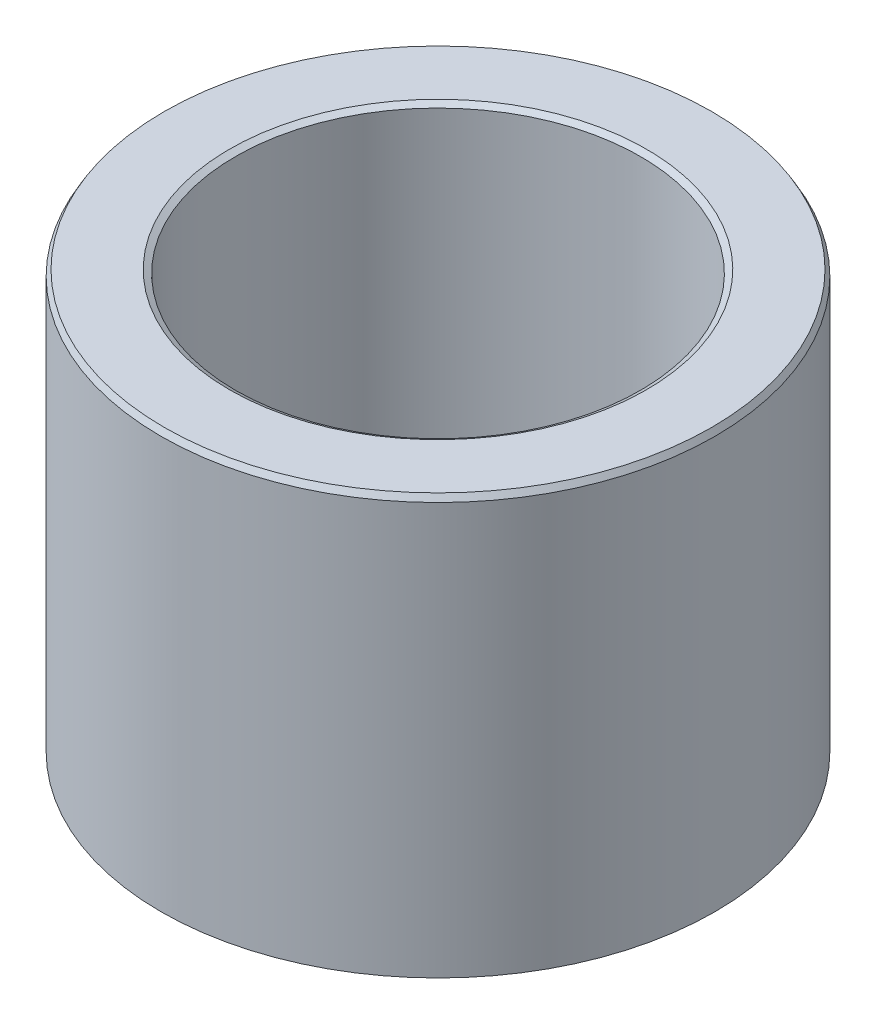
SolidWorks part; units mm, degrees
ref_plane "Front Plane" through (0, 0, 0) normal (0, 0, 1) x (1, 0, 0)
ref_plane "Top Plane" through (0, 0, 0) normal (0, 1, 0) x (1, 0, 0)
ref_plane "Right Plane" through (0, 0, 0) normal (1, 0, 0) x (0, 0, -1)
sketch "Sketch1" plane through (0, 0, 0) normal (0, 1, 0) x (1, 0, 0)
  circle A0 centre (0, 0) radius 42.5
  dimension "SLEEVE_OD" = 85
extrude "Boss-Extrude1" add sketch "Sketch1" along normal blind 64.588
sketch "Sketch2" plane through (0, 0, 0) normal (0, 1, 0) x (1, 0, 0)
  circle A0 centre (0, 0) radius 31.0636
  dimension "BORE_D" = 62.1272
extrude "Cut-Extrude1" cut sketch "Sketch2" along normal through all
chamfer "Chamfer1" distance 0.9093 angle 30 4 edges at (0, 64.588, 31.0636) (0, 0, 31.0636) (0, 0, 42.5) (0, 64.588, 42.5) first distance on face at (0, 64.588, 31.0636) first distance on face at (0, 0, 31.0636) first distance on face at (0, 64.588, 42.5)
